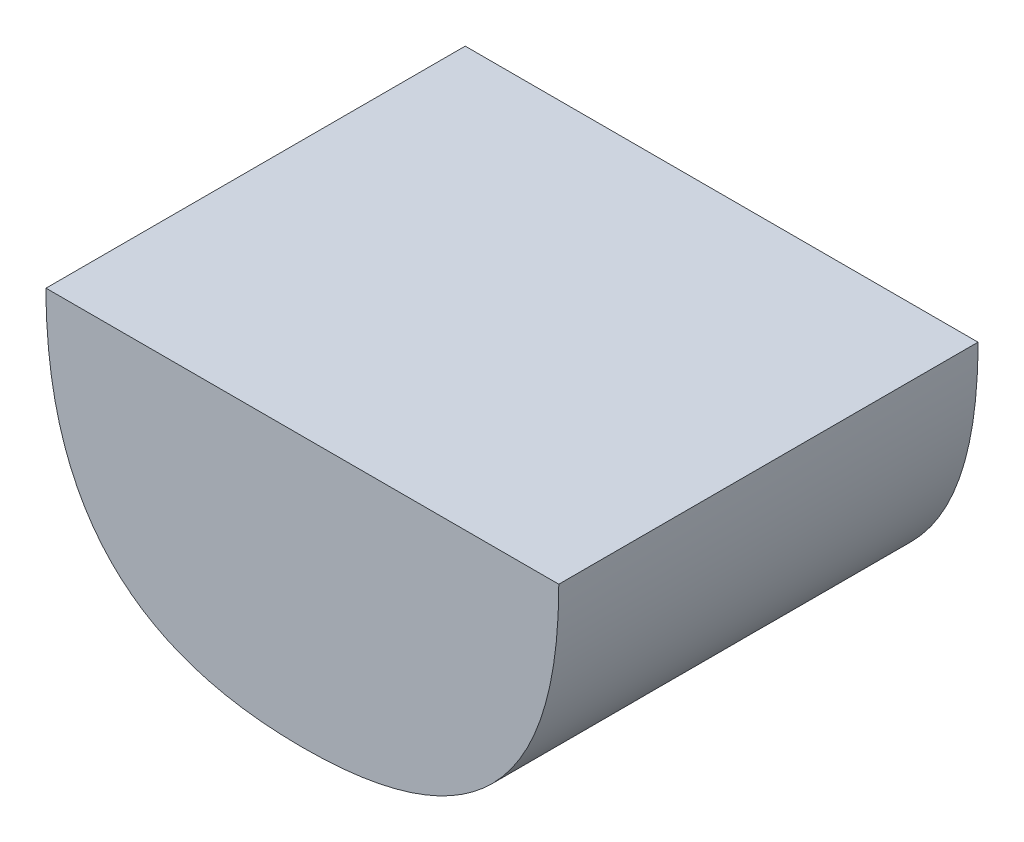
SolidWorks part; units mm, degrees
ref_plane "Front Plane" through (0, 0, 0) normal (0, 0, 1) x (1, 0, 0)
ref_plane "Top Plane" through (0, 0, 0) normal (0, 1, 0) x (1, 0, 0)
ref_plane "Right Plane" through (0, 0, 0) normal (1, 0, 0) x (0, 0, -1)
sketch "Sketch1" plane through (0, 0, 0) normal (0, 0, 1) x (1, 0, 0)
  line L0 (0, 0) -> (0, 317.813) construction
  line L2 (-302.357, 317.813) -> (302.357, 317.813)
  conic Q0 (0, 0) -> (302.357, 317.813) control (302.357, -0.0664) rho 0.504796
  conic Q1 (0, 0) -> (-302.357, 317.813) control (-302.357, -0.0664) rho 0.504796
extrude "Boss-Extrude1" add sketch "Sketch1" against normal blind 494.3856 contours L2 Q0 Q1
